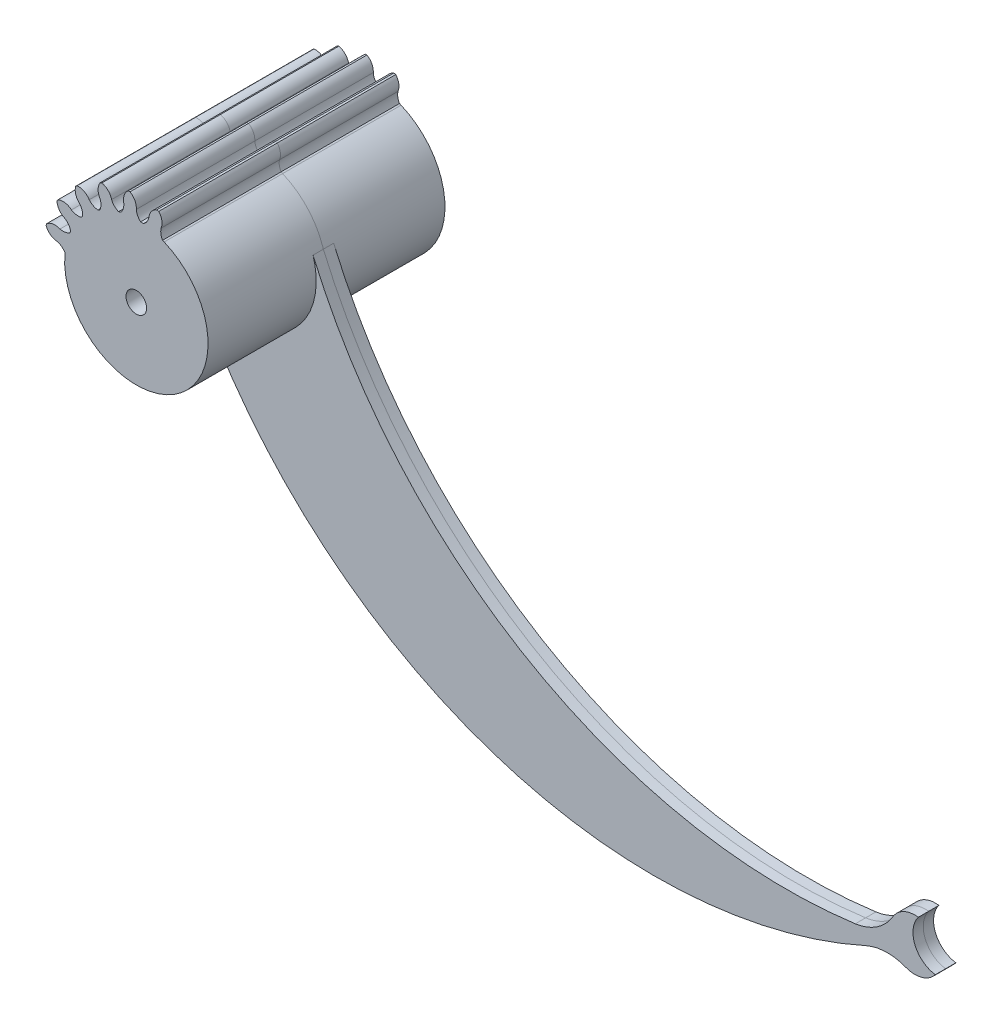
SolidWorks part; units mm, degrees
ref_plane "Plan de face" through (0, 0, 0) normal (0, 0, 1) x (1, 0, 0)
ref_plane "Plan de dessus" through (0, 0, 0) normal (0, 1, 0) x (1, 0, 0)
ref_plane "Plan de droite" through (0, 0, 0) normal (1, 0, 0) x (0, 0, -1)
sketch "Esquisse1" plane through (0, 0, 0) normal (0, 0, 1) x (1, 0, 0)
  circle A0 centre (0, 0) radius 18
extrude "Boss.-Extru.1" add sketch "Esquisse1" against normal blind 23
sketch "Esquisse3" plane through (0, 0, -23) normal (0, 0, -1) x (-1, 0, 0)
  line L0 (-5.4964, 12.79) -> (-5.1005, 12.9694)
  line L1 (-1.4153, 13.9392) -> (-0.828, 13.9392)
  line L2 (3.4609, 13.4999) -> (2.9859, 13.6442)
  line L3 (7.0639, 12.0036) -> (7.4657, 11.7813)
  line L4 (10.417, 9.2257) -> (10.7311, 8.9116)
  line L5 (12.9063, 5.2048) -> (12.7653, 5.634)
  line L6 (13.8895, 0.9713) -> (13.8895, 1.4478)
  arc A0 (-7.2352, 14.2707) -> (15.9996, 0.1072) centre (0, 0) ccw
  arc A2 (3.4609, 13.4999) -> (4.9239, 15.2235) centre (2.4924, 15.8047) ccw
  arc A3 (7.0585, 13.9223) -> (7.2352, 14.2707) centre (4.9239, 15.2235) ccw
  arc A4 (7.4657, 11.7813) -> (9.3698, 12.9694) centre (7.2352, 14.2707) ccw
  arc A5 (11.0004, 11.0744) -> (9.4294, 15.4687) centre (9.3698, 12.9694) ccw
  arc A6 (10.7311, 8.9116) -> (12.9063, 9.4565) centre (11.2757, 11.3516) ccw
  arc A7 (13.8747, 7.1517) -> (13.7322, 11.8162) centre (12.9063, 9.4565) ccw
  arc A8 (12.9063, 5.2048) -> (15.1902, 5.0258) centre (14.2219, 7.3307) ccw
  arc A9 (-0.828, 13.9392) -> (0, 16) centre (-2.4924, 15.8047) ccw
  arc A10 (-2.4315, 15.4188) -> (-6.9047, 16.7487) centre (-4.9239, 15.2235) ccw
  arc A11 (-5.1005, 12.9694) -> (-4.9239, 15.2235) centre (-7.2352, 14.2707) ccw
  arc A12 (-7.0585, 13.9223) -> (-9.4294, 15.4687) centre (-9.3698, 12.9694) ccw
  arc A13 (15.4022, 2.5348) -> (16.7021, 7.0168) centre (15.1902, 5.0258) ccw
  arc A14 (13.8895, 0.9713) -> (15.9996, 0.1072) centre (15.7876, 2.5982) ccw
  arc A15 (15.7876, 2.5982) -> (13.8895, 1.4478) centre (15.9996, 0.1072) ccw
  arc A16 (18.0699, -1.2942) -> (15.609, 0.1046) centre (15.821, -2.3864) ccw
  arc A17 (-7.2352, 14.2707) -> (-5.4964, 12.79) centre (-4.9239, 15.2235) ccw
  arc A18 (-6.9047, 16.7487) -> (-9.4294, 15.4687) centre (-7.2352, 14.2707) ccw
  arc A19 (-2.4924, 15.8047) -> (-1.4153, 13.9392) centre (0, 16) ccw
  arc A20 (-1.4153, 18.0608) -> (-4.8037, 14.8519) centre (-2.4924, 15.8047) ccw
  arc A21 (-2.4924, 15.8047) -> (-4.9239, 15.2235) centre (0, 0) ccw
  arc A22 (1.4153, 18.0608) -> (-1.4153, 18.0608) centre (0, 16) ccw
  arc A24 (7.0585, 13.9223) -> (4.2114, 17.6199) centre (4.9239, 15.2235) ccw
  arc A25 (3.4609, 13.4999) -> (4.9239, 15.2235) centre (2.4924, 15.8047) ccw
  arc A26 (-2.4924, 15.8047) -> (-1.4153, 13.9392) centre (0, 16) ccw
  arc A27 (2.4315, 15.4188) -> (-1.4153, 18.0608) centre (0, 16) ccw
  arc A28 (2.4924, 15.8047) -> (2.9859, 13.6442) centre (4.9239, 15.2235) ccw
  arc A29 (4.2114, 17.6199) -> (0, 15.6094) centre (2.4924, 15.8047) ccw
  arc A30 (4.2114, 17.6199) -> (0, 15.6094) centre (2.4924, 15.8047) ccw
  arc A31 (2.4924, 15.8047) -> (0, 16) centre (0, 0) ccw
  arc A32 (7.2352, 14.2707) -> (7.0639, 12.0036) centre (9.3698, 12.9694) ccw
  arc A33 (9.4294, 15.4687) -> (4.8037, 14.8519) centre (7.2352, 14.2707) ccw
  arc A34 (11.2757, 11.3516) -> (10.417, 9.2257) centre (12.9063, 9.4565) ccw
  arc A35 (13.7322, 11.8162) -> (9.1411, 12.6528) centre (11.2757, 11.3516) ccw
  arc A36 (7.2352, 14.2707) -> (4.9239, 15.2235) centre (0, 0) ccw
  arc A37 (11.2757, 11.3516) -> (9.3698, 12.9694) centre (0, 0) ccw
  arc A38 (14.2219, 7.3307) -> (12.7653, 5.634) centre (15.1902, 5.0258) ccw
  arc A39 (14.2219, 7.3307) -> (12.9063, 9.4565) centre (0, 0) ccw
  arc A40 (16.7021, 7.0168) -> (12.5913, 9.2257) centre (14.2219, 7.3307) ccw
  arc A41 (18.0509, 1.5363) -> (14.8193, 4.9031) centre (15.7876, 2.5982) ccw
  arc A42 (15.7876, 2.5982) -> (15.1902, 5.0258) centre (0, 0) ccw
  arc A43 (18.0699, -1.2942) -> (18.0509, 1.5363) centre (15.9996, 0.1072) ccw
  circle A44 centre (0, 0) radius 2
  circle A45 centre (0, 0) radius 13.9234
  circle M5 centre (0, 0) radius 18
extrude "Enlèv. mat.-Extru.3" cut sketch "Esquisse3" against normal through all contours A20 A12 A17 L0 A11 M5 | A20 A10 A18 A12 M5 | A29 A10 A19 L1 A9 M5 | A29 A22 A20 A10 M5 | A33 A27 A28 L2 A2 M5 | A33 A24 A29 A27 M5 | A35 A24 A3 A32 L3 A4 M5 | A35 A5 A33 A24 M5 | A40 A5 A34 L4 A6 M5 | A40 A7 A35 A5 M5 | A41 A7 A38 L5 A8 M5 | A41 A13 A40 A7 M5 | A16 A13 A15 L6 A14 M5 | A16 A43 A41 A13 M5 | A44 | A16 A0 A12 M5 | A45 A17 A0 A14 | A12 A17 | A14 A16 region at (6.2457, 15.1501, -23) region at (7.8998, -11.9964, -23) region at (-12.4217, 10.6886, -23) region at (7.1468, 14.0965, -23) region at (8.5837, -14.0813, -23) region at (-16.3294, 1.3898, -23) region at (-15.1085, 6.3472, -23) region at (-15.8043, 0.1059, -23) region at (9.3193, 15.5258, -23) region at (1.2806, 16.3434, -23) region at (-11.8123, 13.7243, -23) region at (-8.5298, 13.993, -23) region at (-18.0486, -0.5533, -23) region at (2.8729, 18.2178, -23) region at (-11.624, 13.8843, -23) region at (-16.3935, 8.45, -23) region at (-2.8729, 18.2177, -23) region at (-3.81, 15.9403, -23) region at (0, 0, -23)
sketch "Esquisse4" plane through (0, 0, -23) normal (0, 0, -1) x (-1, 0, 0)
  line L0 (6.8604, 16.6414) -> (0, 0) construction
  line L1 (-130.1688, -53.4545) -> (-92.4244, 38.1021) construction
  line L2 (0, 0) -> (-5.3067, -12.8724) construction
  line L3 (12.8724, -5.3067) -> (0, 0) construction
  line L4 (0, 0) -> (-12.8724, 5.3067) construction
  line L5 (-12.8724, 5.3067) -> (-597.4932, 246.3176) construction
  line L6 (-130.1688, -53.4545) -> (-191.9541, -27.9834) construction
  arc A0 (7.03, 16.5704) -> (6.6901, 16.7105) centre (0, 0) ccw construction
  arc A3 (-5.4019, 12.8328) -> (13.8895, 0.9713) centre (0, 0) ccw construction
  circle A4 centre (-105.26, 43.3936) radius 100
  circle A5 centre (-79.5888, 32.8106) radius 100
  circle A6 centre (-130.1688, -53.4545) radius 5
  circle A7 centre (-134.7914, -51.5488) radius 5
  point P4 (-130.1688, -53.4545)
  arc M8 (-5.4019, 12.8328) -> (13.8895, 0.9713) centre (0, 0) ccw
  dimension "D2" = 90
  dimension "D1" = 90
extrude "Boss.-Extru.2" add sketch "Esquisse4" against normal blind 2 separate body contours A6 A5 A4 M8 | A7 A6 A5 | A7 A4 A6 | A5 A6 A4 region at (42.9441, -42.0103, -23) region at (129.7606, -56.3767, -23) region at (127.8441, -51.6173, -23) region at (127.0738, -54.663, -23)
mirror "Symétrie1" about plane through (0, 0, -23) normal (0, 0, 1) of bodies 104 108
fillet "Congé1" radius 10 2 edges at (125.2968, -54.5785, -22) (125.7936, -55.8748, -22)
fillet "Congé2" radius 10 2 edges at (125.2968, -54.5785, -24) (125.7936, -55.8748, -24)
